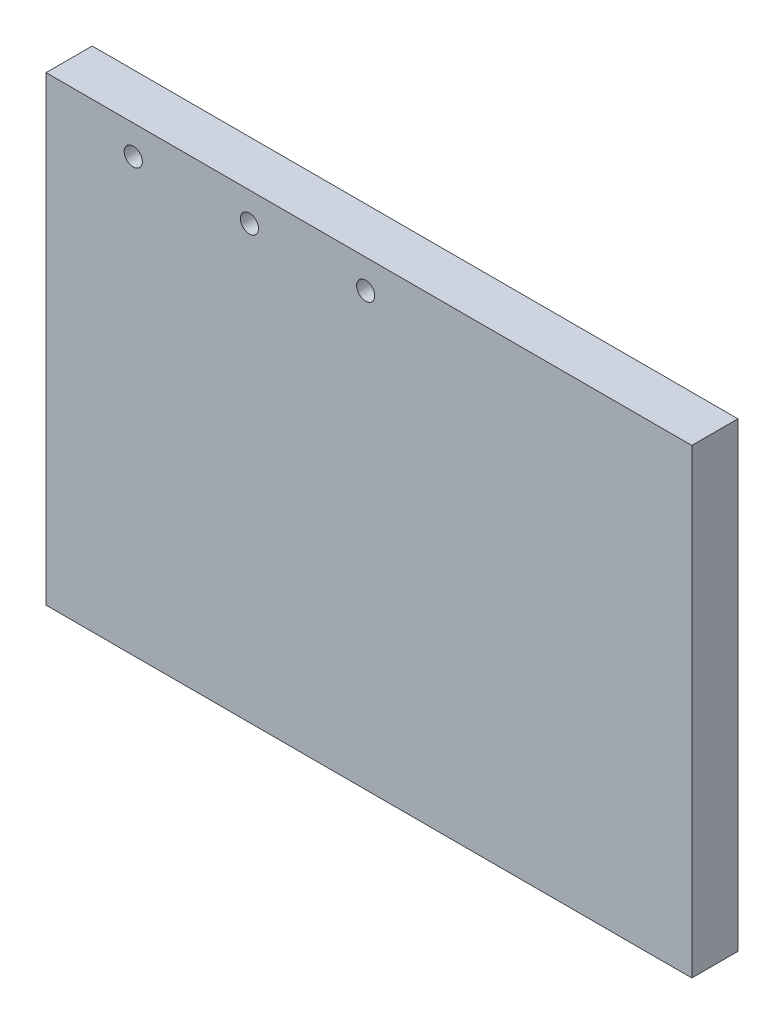
SolidWorks part; units mm, degrees
material "Balsa"
ref_plane "Front Plane" through (0, 0, 0) normal (0, 0, 1) x (1, 0, 0)
ref_plane "Top Plane" through (0, 0, 0) normal (0, 1, 0) x (1, 0, 0)
ref_plane "Right Plane" through (0, 0, 0) normal (1, 0, 0) x (0, 0, -1)
sketch "Sketch1" plane through (0, 0, 0) normal (0, 0, 1) x (1, 0, 0)
  line L1 (-44.45, 31.75) -> (44.45, 31.75)
  line L2 (-44.45, 31.75) -> (-44.45, -31.75)
  line L3 (-44.45, -31.75) -> (44.45, -31.75)
  line L4 (44.45, 31.75) -> (44.45, -31.75)
  line L5 (-44.45, 31.75) -> (44.45, -31.75) construction
  line L6 (-44.45, -31.75) -> (44.45, 31.75) construction
  point P0 (0, 0)
  dimension "D5" = 88.9
  dimension "D6" = 63.5
extrude "Boss-Extrude1" add sketch "Sketch1" along normal blind 6.35 contours L4 L1 L2 L3 region at (0, 0, 0)
sketch "Sketch2" plane through (0, 0, 0) normal (0, 0, -1) x (-1, 0, 0)
  line L0 (44.45, 31.75) -> (-44.45, 31.75) construction
  line L1 (44.45, 31.75) -> (32.45, 31.75) construction
  line L2 (44.45, 31.75) -> (44.45, 27.75) construction
  line L3 (44.45, 27.75) -> (32.45, 27.75) construction
  line L4 (32.45, 31.75) -> (32.45, 27.75) construction
  line L5 (44.45, 31.75) -> (44.45, -31.75) construction
  line L6 (32.45, 27.75) -> (0.45, 27.75) construction
  circle A0 centre (0.45, 27.75) radius 1.25
  circle A1 centre (32.45, 27.75) radius 1.25
  circle A2 centre (16.45, 27.75) radius 1.25
  dimension "D4" = 2.5
  dimension "D1" = 4
  dimension "D2" = 12
  dimension "D3" = 16
extrude "Cut-Extrude1" cut sketch "Sketch2" against normal through all
